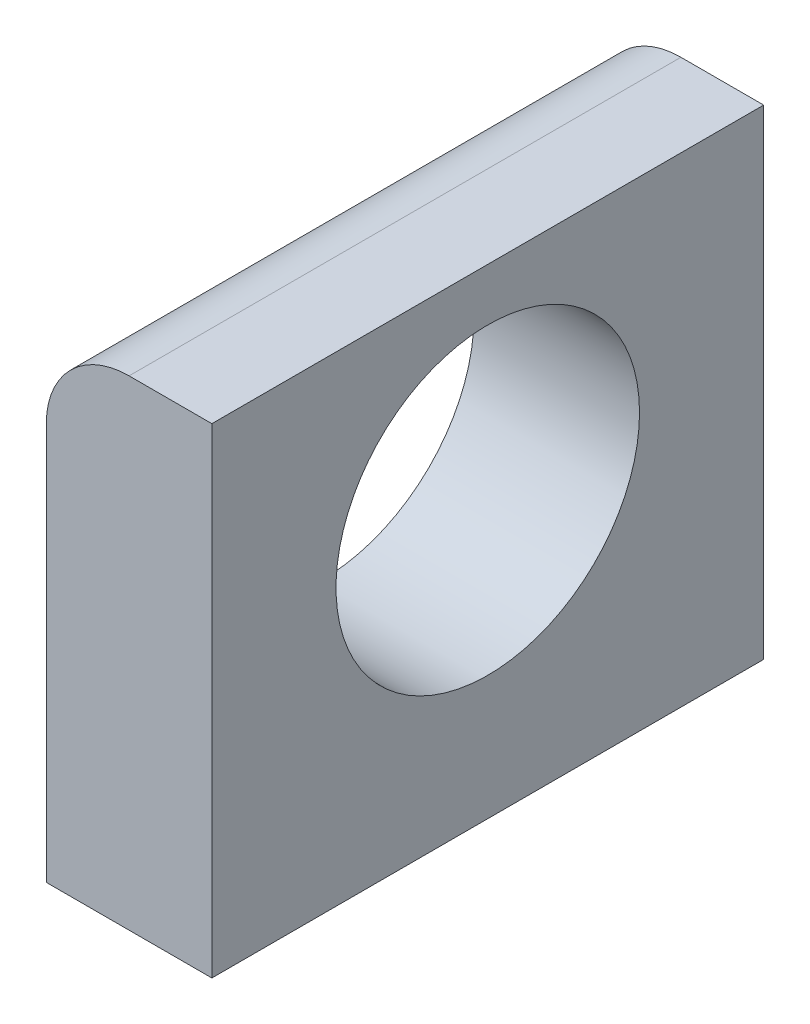
SolidWorks part; units mm, degrees
material "ABS"
ref_plane "前视基准面" through (0, 0, 0) normal (0, 0, 1) x (1, 0, 0)
ref_plane "上视基准面" through (0, 0, 0) normal (0, 1, 0) x (1, 0, 0)
ref_plane "右视基准面" through (0, 0, 0) normal (1, 0, 0) x (0, 0, -1)
sketch "草图1" plane through (0, 0, 0) normal (0, 0, 1) x (1, 0, 0)
  line L1 (-1.5, -4.35) -> (1.5, -4.35)
  line L2 (-1.5, -4.35) -> (-1.5, 4.35)
  line L3 (-1.5, 4.35) -> (1.5, 4.35)
  line L4 (1.5, -4.35) -> (1.5, 4.35)
  line L5 (-1.5, -4.35) -> (1.5, 4.35) construction
  line L6 (-1.5, 4.35) -> (1.5, -4.35) construction
  point P0 (0, 0)
  dimension "D1" = 8.7
  dimension "D2" = 3
extrude "凸台-拉伸1" add sketch "草图1" along normal blind 10
sketch "草图2" plane through (1.5, 0, 0) normal (1, 0, 0) x (0, 0, -1)
  line L0 (-5, 4.35) -> (-5, 0.65) construction
  line L1 (-10, 4.35) -> (0, 4.35) construction
  line L2 (-10, -4.35) -> (0, -4.35) construction
  circle A0 centre (-5, 0.65) radius 2.75
  dimension "D1" = 5.5
  dimension "D2" = 5
extrude "切除-拉伸1" cut sketch "草图2" against normal blind 10
fillet "圆角1" radius 1.5 1 edges at (-1.5, 4.35, 5)
